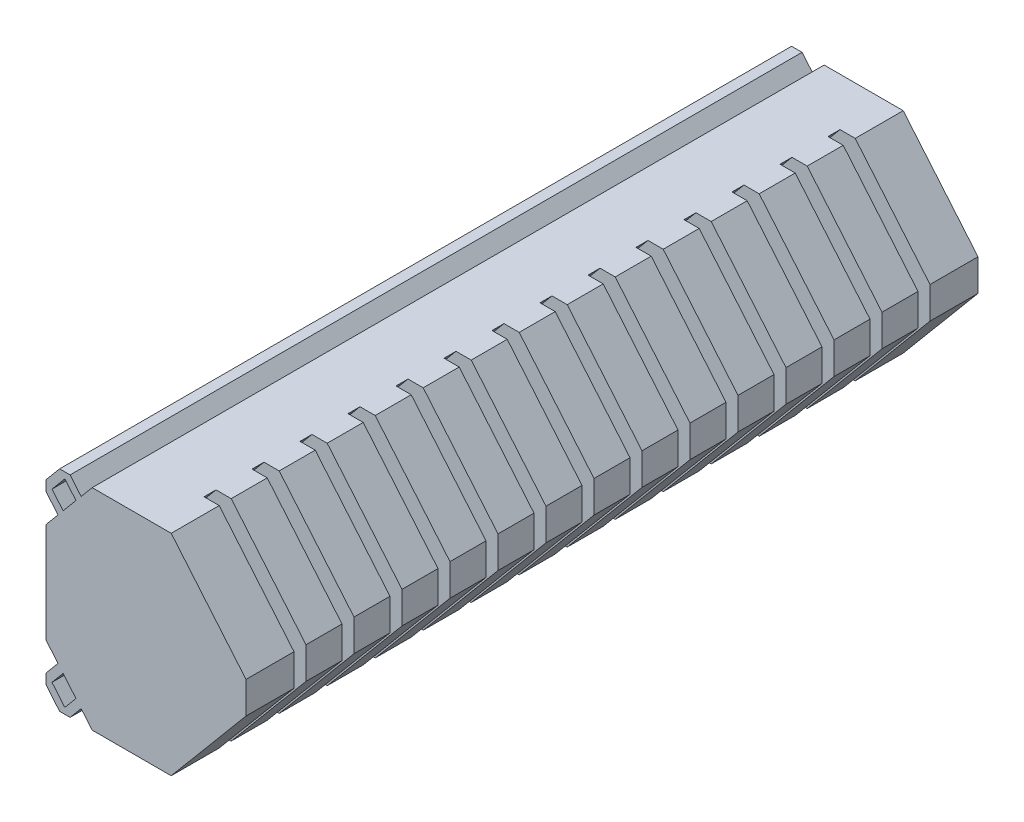
SolidWorks part; units mm, degrees
ref_plane "Ebene vorne" through (0, 0, 0) normal (0, 0, 1) x (1, 0, 0)
ref_plane "Ebene oben" through (0, 0, 0) normal (0, 1, 0) x (1, 0, 0)
ref_plane "Ebene rechts" through (0, 0, 0) normal (1, 0, 0) x (0, 0, -1)
sketch "Skizze3" plane through (0, 0, 0) normal (0, 0, 1) x (1, 0, 0)
  line L0 (-7.7197, 0) -> (0, 9.2) construction
  line L1 (0, 9.2) -> (0, -9.2) construction
  line L2 (0, -9.2) -> (-7.7197, 0) construction
  line L3 (-7.5, 0) -> (49992.5, 0) construction
  line L4 (-11, -5) -> (-11, 5)
  line L5 (-11, 5) -> (-6.385, 10.5)
  line L6 (-6.385, 10.5) -> (1.52, 10.5)
  line L7 (1.52, 10.5) -> (9, 1.5857)
  line L13 (0, 9.2) -> (7, 0.8577) construction
  line L14 (7, 0.8577) -> (7, -0.8577) construction
  line L15 (7, -0.8577) -> (0, -9.2) construction
  line L16 (9, 1.5857) -> (9, -1.5857)
  line L17 (-11, -5) -> (-6.385, -10.5)
  line L18 (-6.385, -10.5) -> (1.52, -10.5)
  line L19 (1.52, -10.5) -> (9, -1.5857)
  point P20 (-11, 0)
  point P23 (9, 0)
  dimension "D2" = 50
  dimension "D3" = 2
  dimension "D4" = 7
  dimension "D5" = 21
  dimension "D1" = 20
  dimension "D6" = 2
  dimension "D7" = 1.3
  dimension "D8" = 10
  dimension "D9" = 50
extrude "Aufsatz-Linear austragen2" add sketch "Skizze3" along normal mid plane 3.6
sketch "Skizze2" plane through (0, 0, 0) normal (0, 0, 1) x (1, 0, 0)
  line L0 (-7.5519, 0) -> (0, 9)
  line L1 (0, 9) -> (0, -9) construction
  line L2 (0, -9) -> (-7.5519, 0)
  line L3 (-7.5, 0) -> (49992.5, 0) construction
  line L13 (0, 9) -> (7, 0.6577)
  line L14 (7, 0.6577) -> (7, -0.6577)
  line L15 (7, -0.6577) -> (0, -9)
  dimension "D2" = 50
  dimension "D4" = 7
  dimension "D5" = 18
  dimension "D1" = 50
extrude "Schnitt-Linear austragen1" cut sketch "Skizze2" against normal mid plane 1
sketch "Skizze5" plane through (0, 0, 0) normal (0, 0, 1) x (1, 0, 0)
  line L0 (-7.5519, 0) -> (-6.7163, 0.9959)
  line L1 (-6.7163, 0.9959) -> (-5.8806, 0)
  line L2 (-5.8806, 0) -> (-6.7163, -0.9959)
  line L3 (-6.7163, -0.9959) -> (-7.5519, 0)
  line L4 (-7.5519, 0) -> (-50007.5519, 0) construction
  line L5 (-7.5519, 0) -> (0, -9)
  line L6 (0, -9) -> (7, -0.6577)
  line L7 (7, -0.6577) -> (7, 0.6577)
  line L8 (7, 0.6577) -> (0, 9)
  line L9 (0, 9) -> (-7.5519, 0)
  line L10 (-7.5519, 0) -> (0, -9) construction
  line L11 (0, -9) -> (7, -0.6577) construction
  line L12 (7, -0.6577) -> (7, 0.6577) construction
  line L13 (7, 0.6577) -> (0, 9) construction
  line L14 (0, 9) -> (-7.5519, 0) construction
  dimension "D2" = 1.3
  dimension "D1" = 0
extrude "Schnitt-Linear austragen2" cut sketch "Skizze5" against normal through all both and the other way through all
sketch "Skizze6" plane through (0, 0, 1.8) normal (0, 0, 1) x (1, 0, 0)
  line L0 (0, 0) -> (50000, 0) construction
  line L2 (-6.7163, 0.9959) -> (-5.8806, 0) construction
  line L3 (-6.385, 10.5) -> (-11, 5) construction
  line L6 (-6.385, 10.5) -> (-11, 5)
  line L7 (-4.5806, -5.041) -> (-4.5806, 5.041)
  line L8 (-4.5806, 5.041) -> (0, 10.5)
  line L9 (-11, 5) -> (-11, -5) construction
  line L13 (-5.8806, 0) -> (-6.7163, -0.9959) construction
  line L14 (-6.7163, 0.9959) -> (-5.8806, 0)
  line L15 (-5.8806, 0) -> (-6.7163, -0.9959)
  line L16 (-6.7163, 0.9959) -> (-7.5519, 0) construction
  line L17 (-7.5519, 0) -> (-6.7163, -0.9959) construction
  line L18 (-6.7163, 0.9959) -> (-7.5519, 0)
  line L19 (-7.5519, 0) -> (-6.7163, -0.9959)
  line L20 (1.52, 10.5) -> (-6.385, 10.5) construction
  line L21 (0, 10.5) -> (-6.385, 10.5)
  line L22 (-4.5806, -5.041) -> (0, -10.5)
  line L23 (0, -10.5) -> (-6.385, -10.5)
  point P11 (-4.5806, 0)
  point P14 (-11, 0)
  point P19 (-4.5806, -5.041)
  line M6 (-6.7163, -0.9959) -> (-7.5519, 0)
  line M7 (-7.5519, 0) -> (-6.7163, 0.9959)
  line M8 (-6.7163, 0.9959) -> (-5.8806, 0)
  line M9 (-5.8806, 0) -> (-6.7163, -0.9959)
  line M10 (-11, -5) -> (-6.385, -10.5)
  line M11 (-6.385, -10.5) -> (1.52, -10.5)
  line M15 (1.52, 10.5) -> (-6.385, 10.5)
  line M16 (-6.385, 10.5) -> (-11, 5)
  line M17 (-11, 5) -> (-11, -5)
  dimension "D2" = 1.3
  dimension "D3" = 11
extrude "Aufsatz-Linear austragen3" add sketch "Skizze6" along normal blind 1.2 contours L0 L22 L7 M17 M10 M11 M9 M6 | L0 L7 L8 M17 M7 M8 M15 M16
pattern_linear "Lineares Muster1" count 15 spacing 4.8 along (0, 0, 1) of "Aufsatz-Linear austragen2", "Schnitt-Linear austragen1", "Schnitt-Linear austragen2", "Aufsatz-Linear austragen3"
sketch "Skizze8" plane through (0, 0, -1.8) normal (0, 0, -1) x (-1, 0, 0)
  line L8 (6.385, -10.5) -> (11, -5)
  line L9 (11, -5) -> (11, 5)
  line L10 (11, 5) -> (6.385, 10.5)
  line L11 (6.385, 10.5) -> (-1.52, 10.5)
  line L12 (-1.52, 10.5) -> (-9, 1.5857)
  line L13 (-9, 1.5857) -> (-9, -1.5857)
  line L14 (-9, -1.5857) -> (-1.52, -10.5)
  line L15 (-1.52, -10.5) -> (6.385, -10.5)
  line L16 (6.385, -10.5) -> (11, -5)
  line L17 (11, -5) -> (11, 5)
  line L18 (11, 5) -> (6.385, 10.5)
  line L19 (6.385, 10.5) -> (-1.52, 10.5)
  line L20 (-1.52, 10.5) -> (-9, 1.5857)
  line L21 (-9, 1.5857) -> (-9, -1.5857)
  line L22 (-9, -1.5857) -> (-1.52, -10.5)
  line L23 (-1.52, -10.5) -> (6.385, -10.5)
  dimension "D1" = 0
extrude "Aufsatz-Linear austragen4" add sketch "Skizze8" along normal blind 1.2 and the other way blind 0.8
sketch "Skizze9" plane through (0, 0, 69) normal (0, 0, 1) x (1, 0, 0)
  line L8 (-4.5806, 5.041) -> (0, 10.5) construction
  line L9 (-4.5806, 5.041) -> (-4.5806, -5.041)
  line L10 (-4.5806, -5.041) -> (-4.5806, 5.041) construction
  line L11 (0, -10.5) -> (1.52, -10.5)
  line L12 (1.52, -10.5) -> (9, -1.5857)
  line L13 (9, -1.5857) -> (9, 1.5857)
  line L14 (9, 1.5857) -> (1.52, 10.5)
  line L15 (1.52, 10.5) -> (0, 10.5)
  line L19 (0, -10.5) -> (1.52, -10.5)
  line L20 (1.52, -10.5) -> (9, -1.5857)
  line L21 (9, -1.5857) -> (9, 1.5857)
  line L22 (9, 1.5857) -> (1.52, 10.5)
  line L23 (1.52, 10.5) -> (0, 10.5)
  line L26 (-4.5806, 5.041) -> (0, 10.5)
  line L27 (-4.5806, -5.041) -> (-4.5806, 5.041)
  line L32 (0, 10.5) -> (-4.5806, 5.041)
  line L33 (-4.5806, -5.041) -> (0, -10.5)
  line L34 (-4.5806, -5.041) -> (0, -10.5)
  dimension "D1" = 0
extrude "Aufsatz-Linear austragen5" add sketch "Skizze9" along normal blind 1.2 and the other way blind 0.8
sketch "Skizze10" plane through (0, 0, -3) normal (0, 0, -1) x (-1, 0, 0)
  line L0 (2.1631, -10.5) -> (50002.1631, -10.5) construction
  line L1 (11, -2.1493) -> (11, -50002.1493) construction
  line L2 (9.1144, -9.9) -> (10.4, -8.3679)
  line L3 (10.4, -8.3679) -> (9.287, -7.0415)
  line L6 (7.4872, -9.1864) -> (8.5894, -10.5)
  line L7 (6.385, -10.5) -> (11, -5) construction
  line L8 (8.5894, -10.5) -> (9.6394, -10.5)
  line L9 (9.6394, -10.5) -> (11, -8.8785)
  line L10 (11, -8.8785) -> (11, -7.8573)
  line L11 (11, -7.8573) -> (9.8012, -6.4286)
  line L12 (7.4872, -9.1864) -> (8.0014, -8.5736)
  line L13 (7.8288, -8.3679) -> (7.3146, -8.9807) construction
  line L14 (7.4856, -6.4268) -> (32146.8661, -38308.6489) construction
  line L15 (9.1144, -6.8358) -> (9.6287, -6.223) construction
  line L16 (9.8012, -6.4286) -> (9.287, -7.0415)
  line L17 (8.0014, -8.5736) -> (7.8288, -8.3679) construction
  line L18 (7.8288, -8.3679) -> (9.1144, -6.8358) construction
  line L19 (9.1144, -6.8358) -> (9.287, -7.0415) construction
  line L20 (9.7572, -9.134) -> (8.4716, -7.6019) construction
  line L21 (8.0014, -8.5736) -> (9.1144, -9.9)
  line L22 (10.4, -8.3679) -> (10.9142, -8.9807) construction
  point P27 (9.1144, -8.3679)
  dimension "D1" = 2
  dimension "D2" = 0.6
  dimension "D3" = 0.6
  dimension "D4" = 0.8
  dimension "D5" = 50
  dimension "D6" = 0.8
extrude "Aufsatz-Linear austragen6" add sketch "Skizze10" against normal up to surface (73.2 mm away) contours L21 L2 L3 L16 L11 L10 L9 L8 L6 L12 up to face at (-1.7162, 0, 70.2)
mirror "Spiegeln1" about plane through (0, 0, 0) normal (0, 1, 0) of "Aufsatz-Linear austragen6"
sketch "Skizze11" plane through (-11, 0, 0) normal (-1, 0, 0) x (0, 0, 1)
  line L0 (70.2, 7.0415) -> (-3, 7.0415) construction
  line L1 (70.2, 7.0415) -> (-3, 7.0415) construction
  line L2 (70.2, 8.5736) -> (-3, 8.5736) construction
  line L3 (-3, 8.8785) -> (-3, 7.8573) construction
  line L4 (70.2, 9.9) -> (-3, 9.9) construction
  line L6 (-1.7, 8.4707) -> (-0.5007, 9.9)
  line L7 (-0.5007, 9.9) -> (0.6986, 8.4707)
  line L8 (0.6986, 8.4707) -> (-0.5007, 7.0415)
  line L9 (-0.5007, 7.0415) -> (-1.7, 8.4707)
  line L11 (0, 0) -> (50000, 0) construction
  line L12 (33.6, -3.1716) -> (33.6, -50003.1716) construction
  line L13 (70.2, -5) -> (-3, -5) construction
  line L14 (-0.5007, -7.0415) -> (-1.7, -8.4707)
  line L15 (-1.7, -8.4707) -> (-0.5007, -9.9)
  line L16 (-0.5007, -9.9) -> (0.6986, -8.4707)
  line L17 (0.6986, -8.4707) -> (-0.5007, -7.0415)
  line L18 (66.5014, -8.4707) -> (67.7007, -7.0415)
  line L19 (67.7007, -9.9) -> (66.5014, -8.4707)
  line L20 (68.9, -8.4707) -> (67.7007, -9.9)
  line L21 (67.7007, -7.0415) -> (68.9, -8.4707)
  line L22 (67.7007, 7.0415) -> (68.9, 8.4707)
  line L23 (68.9, 8.4707) -> (67.7007, 9.9)
  line L24 (67.7007, 9.9) -> (66.5014, 8.4707)
  line L25 (66.5014, 8.4707) -> (67.7007, 7.0415)
  line L26 (70.2, 8.5736) -> (-3, 8.5736) construction
  line L27 (70.2, 9.9) -> (-3, 9.9) construction
  line L29 (70.2, 8.3679) -> (-3, 8.3679) construction
  line L30 (70.2, 8.3679) -> (-3, 8.3679) construction
  circle A0 centre (67.7007, 8.4707) radius 0.9187 construction
  point P19 (33.6, -5)
  dimension "D2" = 1.8374
  dimension "D1" = 1.3
  dimension "D3" = 50
  dimension "D4" = 50
extrude "Schnitt-Linear austragen4" cut sketch "Skizze11" against normal up to next
sketch "Skizze12" plane through (0, 0, 70.2) normal (0, 0, 1) x (1, 0, 0)
  line L0 (-5.8806, 0) -> (-6.7163, -0.9959) construction
  line L1 (-6.7163, -0.9959) -> (-7.5519, 0) construction
  line L2 (-7.5519, 0) -> (-6.7163, 0.9959) construction
  line L3 (-6.7163, 0.9959) -> (-5.8806, 0) construction
  line L4 (-5.8806, 0) -> (-6.7163, -0.9959)
  line L5 (-6.7163, -0.9959) -> (-7.5519, 0)
  line L6 (-7.5519, 0) -> (-6.7163, 0.9959)
  line L7 (-6.7163, 0.9959) -> (-5.8806, 0)
extrude "Aufsatz-Linear austragen7" add sketch "Skizze12" against normal up to vertex (3.5 mm away)
